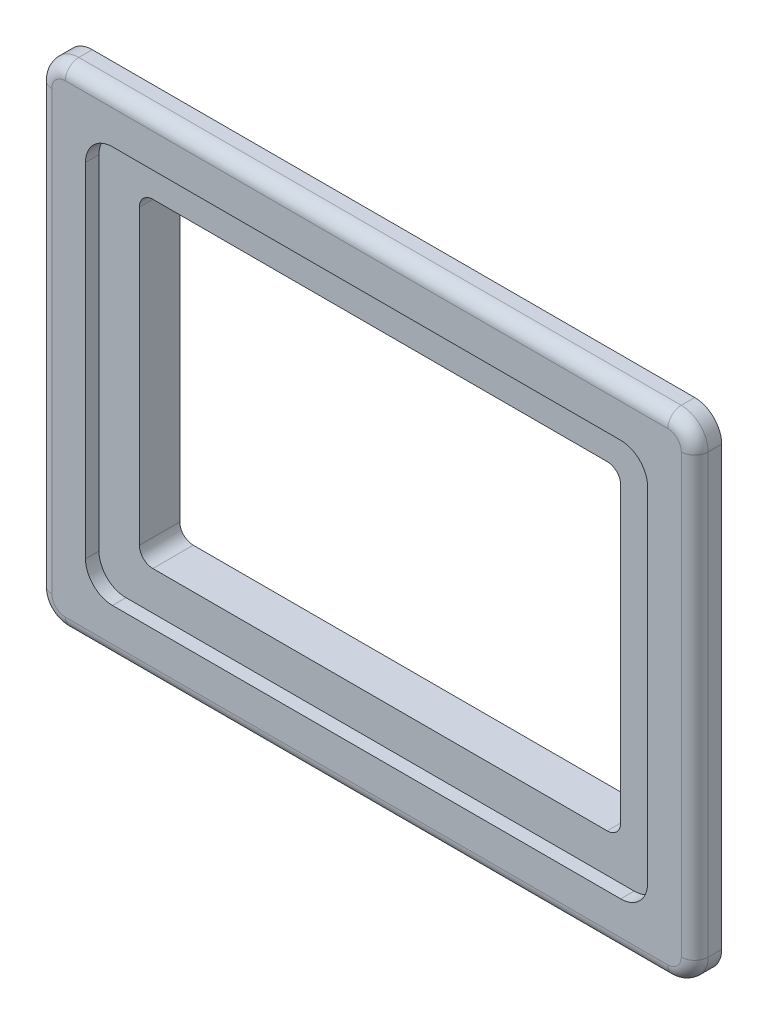
SolidWorks part; units mm, degrees
material "ABS"
ref_plane "Front Plane" through (0, 0, 0) normal (0, 0, 1) x (1, 0, 0)
ref_plane "Top Plane" through (0, 0, 0) normal (0, 1, 0) x (1, 0, 0)
ref_plane "Right Plane" through (0, 0, 0) normal (1, 0, 0) x (0, 0, -1)
sketch "Sketch1" plane through (0, 0, 0) normal (0, 0, 1) x (1, 0, 0)
  line L1 (-154.7812, -115.8875) -> (154.7812, -115.8875)
  line L2 (-154.7812, -115.8875) -> (-154.7812, 115.8875)
  line L3 (-154.7812, 115.8875) -> (154.7812, 115.8875)
  line L4 (154.7812, -115.8875) -> (154.7812, 115.8875)
  line L5 (-154.7812, -115.8875) -> (154.7812, 115.8875) construction
  line L6 (-154.7812, 115.8875) -> (154.7812, -115.8875) construction
  line L11 (-100.7138, -75.4062) -> (100.7138, 75.4063) construction
  line L12 (-100.7138, 75.4063) -> (100.7138, -75.4062) construction
  line L13 (-113.5063, -75.4063) -> (113.5062, -75.4063)
  line L14 (-113.5063, -75.4063) -> (-113.5063, 75.4062)
  line L15 (-113.5063, 75.4062) -> (113.5062, 75.4062)
  line L16 (113.5062, -75.4063) -> (113.5062, 75.4062)
  line L17 (-113.5063, -75.4063) -> (113.5062, 75.4062) construction
  line L18 (-113.5063, 75.4062) -> (113.5062, -75.4063) construction
  line L19 (-132.5562, -93.6625) -> (132.5562, -93.6625)
  line L20 (-132.5562, -93.6625) -> (-132.5562, 93.6625)
  line L21 (-132.5562, 93.6625) -> (132.5562, 93.6625)
  line L22 (132.5562, -93.6625) -> (132.5562, 93.6625)
  line L23 (-132.5562, -93.6625) -> (132.5562, 93.6625) construction
  line L24 (-132.5562, 93.6625) -> (132.5562, -93.6625) construction
  point P0 (0, 0)
  point P6 (0, 0)
  point P11 (0, 0)
  point P16 (0, 0)
  dimension "D1" = 309.5625
  dimension "D2" = 231.775
  dimension "D3" = 227.0125
  dimension "D4" = 150.8125
  dimension "D5" = 265.1125
  dimension "D6" = 187.325
extrude "Boss-Extrude1" add sketch "Sketch1" along normal blind 12.7 contours L1 L4 L3 L2 L22 L19 L20 L21 | L19 L22 L21 L20 L16 L13 L14 L15 region at (-150.9141, 0, 0) region at (-129.3101, 0, 0)
extrude "Boss-Extrude2" add sketch "Sketch1<3>" against normal blind 12.7 contours L19 L22 L21 L20 L16 L13 L14 L15 region at (-129.3101, 0, 0)
sketch "Sketch1<3>" plane through (0, 0, 0) normal (0, 0, 1) x (1, 0, 0) same geometry as "Sketch1"
fillet "Fillet1" radius 12.7 8 edges at (132.5562, -93.6625, -6.35) (132.5562, 93.6625, -6.35) (-132.5562, 93.6625, -6.35) (-132.5562, -93.6625, -6.35) (154.7812, 115.8875, 6.35) (154.7812, -115.8875, 6.35) (-154.7812, 115.8875, 6.35) (-154.7812, -115.8875, 6.35)
extrude "Cut-Extrude1" cut sketch "Sketch1<4>" along direction (0, 0, 1) on the side against the normal blind 6.35 from surface contours L19 L22 L21 L20 L16 L13 L14 L15 region at (-129.3101, 0, 0) starting at face at (0, 0, 12.7)
sketch "Sketch1<4>" plane through (0, 0, 0) normal (0, 0, 1) x (1, 0, 0) same geometry as "Sketch1"
fillet "Fillet2" radius 6.35 4 edges at (113.5062, -75.4063, -3.175) (-113.5063, -75.4063, -3.175) (113.5062, 75.4062, -3.175) (-113.5063, 75.4062, -3.175)
fillet "Fillet3" radius 12.7 4 edges at (132.5562, 93.6625, 9.525) (132.5562, -93.6625, 9.525) (-132.5562, -93.6625, 9.525) (-132.5562, 93.6625, 9.525)
fillet "Fillet4" radius 6.35 8 edges at (-151.0615, -112.1678, 12.7) (0, -115.8875, 12.7) (151.0615, -112.1678, 12.7) (154.7812, 0, 12.7) (151.0615, 112.1678, 12.7) (0, 115.8875, 12.7) (-151.0615, 112.1678, 12.7) (-154.7812, 0, 12.7)
